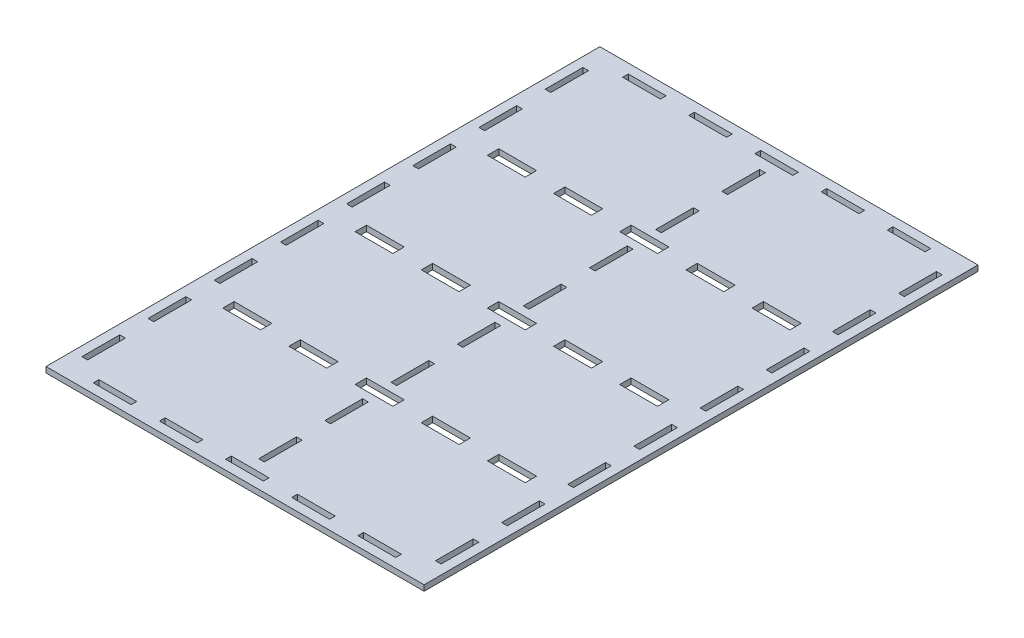
SolidWorks part; units mm, degrees
ref_plane "Front Plane" through (0, 0, 0) normal (0, 0, 1) x (1, 0, 0)
ref_plane "Top Plane" through (0, 0, 0) normal (0, 1, 0) x (1, 0, 0)
ref_plane "Right Plane" through (0, 0, 0) normal (1, 0, 0) x (0, 0, -1)
sketch "Sketch1" plane through (0, 0, 0) normal (0, 1, 0) x (1, 0, 0)
  line L1 (0, 0) -> (200, 0)
  line L2 (0, 0) -> (0, 293)
  line L3 (0, 293) -> (200, 293)
  line L4 (200, 0) -> (200, 293)
  line L5 (0, 0) -> (200, 293) construction
  line L6 (0, 293) -> (200, 0) construction
  line L7 (20, 288) -> (40, 288)
  line L8 (20, 288) -> (20, 285)
  line L9 (20, 285) -> (40, 285)
  line L10 (40, 288) -> (40, 285)
  line L11 (20, 288) -> (40, 285) construction
  line L12 (20, 285) -> (40, 288) construction
  line L13 (5, 279) -> (8, 279)
  line L14 (5, 279) -> (5, 259)
  line L15 (5, 259) -> (8, 259)
  line L16 (8, 279) -> (8, 259)
  line L17 (5, 279) -> (8, 259) construction
  line L18 (5, 259) -> (8, 279) construction
  line L38 (0, 146.5) -> (200, 146.5) construction
  line L39 (100, 293) -> (100, 0) construction
  point P10 (30, 286.5)
  point P15 (6.5, 269)
  dimension "D1" = 293
  dimension "D2" = 200
  dimension "D3" = 3
  dimension "D4" = 20
  dimension "D5" = 5
  dimension "D6" = 5
  dimension "D7" = 14
  dimension "D8" = 20
extrude "Boss-Extrude1" add sketch "Sketch1" along normal blind 3 contours L1 L4 L3 L2 L7 L10 L9 L8 L13 L16 L15 L14 | L10 L7 L8 L9 | L16 L13 L14 L15 region at (100.1677, 0, -146.2307) region at (30, 0, -286.5) region at (6.5, 0, -269)
sketch "Sketch2" plane through (0, 3, 0) normal (0, 1, 0) x (1, 0, 0)
  line L0 (5, 259) -> (8, 259) construction
  line L1 (8, 279) -> (8, 259) construction
  line L2 (5, 279) -> (5, 259) construction
  line L3 (5, 279) -> (8, 279) construction
  line L4 (8, 279) -> (5, 279)
  line L5 (8, 259) -> (8, 279)
  line L6 (5, 259) -> (8, 259)
  line L7 (5, 279) -> (5, 259)
  line L8 (8, 279) -> (5, 279)
  line L9 (8, 259) -> (8, 279)
  line L10 (5, 259) -> (8, 259)
  line L11 (5, 279) -> (5, 259)
  line L12 (40, 288) -> (20, 288)
  line L13 (40, 285) -> (40, 288)
  line L14 (20, 285) -> (40, 285)
  line L15 (20, 288) -> (20, 285)
  line L16 (40, 288) -> (20, 288)
  line L17 (40, 285) -> (40, 288)
  line L18 (20, 285) -> (40, 285)
  line L19 (20, 288) -> (20, 285)
  line L20 (0, 0) -> (200, 0)
  line L21 (200, 0) -> (200, 293)
  line L22 (200, 293) -> (0, 293)
  line L23 (0, 293) -> (0, 0)
  line L24 (0, 0) -> (200, 0)
  line L25 (200, 0) -> (200, 293)
  line L26 (200, 293) -> (0, 293)
  line L27 (0, 293) -> (0, 0)
  line L28 (20, 288) -> (20, 285) construction
  line L29 (40, 288) -> (40, 285) construction
  line L30 (20, 285) -> (40, 285) construction
  line L31 (20, 288) -> (40, 288) construction
  line L32 (5, 259) -> (8, 259)
  line L33 (8, 279) -> (8, 259)
  line L34 (5, 279) -> (5, 259)
  line L35 (5, 279) -> (8, 279)
  line L36 (20, 288) -> (20, 285)
  line L37 (40, 288) -> (40, 285)
  line L38 (20, 285) -> (40, 285)
  line L39 (20, 288) -> (40, 288)
  dimension "D1" = 0
  dimension "D2" = 0
  dimension "D3" = 0
extrude "Cut-Extrude2" cut sketch "Sketch2" against normal blind 10 contours L16 L19 L18 L17 | L8 L11 L10 L9 region at (6.5, 3, -269) region at (30, 3, -286.5)
pattern_linear "LPattern3" count 5 spacing 35 along (1, 0, 0) count 5 spacing 70 along (0, 0, 1) of face at (30, 1.5, -285) of face at (20, 1.5, -286.5) of face at (30, 1.5, -288) of face at (40, 1.5, -286.5)
pattern_linear "LPattern4" count 3 spacing 93.5 along (1, 0, 0) count 8 spacing 35 along (0, 0, 1) of face at (5, 1.5, -269) of face at (8, 1.5, -269) of face at (6.5, 1.5, -279) of face at (6.5, 1.5, -259)
sketch "Sketch4" plane through (0, 3, 0) normal (0, 1, 0) x (1, 0, 0)
  line L0 (20, 215) -> (40, 215) construction
  line L1 (6.5, 286.5) -> (100, 286.5)
  line L2 (6.5, 286.5) -> (6.5, 216.5)
  line L3 (6.5, 216.5) -> (100, 216.5)
  line L4 (100, 286.5) -> (100, 216.5)
  line L5 (20, 8) -> (20, 5) construction
  line L6 (5, 224) -> (8, 224) construction
  line L7 (100, 293) -> (100, 0) construction
  line L8 (40, 215) -> (40, 218) construction
  line L9 (6.5, 216.5) -> (100, 216.5)
  line L10 (6.5, 216.5) -> (6.5, 146.5)
  line L11 (6.5, 146.5) -> (100, 146.5)
  line L12 (100, 216.5) -> (100, 146.5)
  line L13 (20, 218) -> (20, 215) construction
  line L14 (40, 218) -> (20, 218) construction
  line L15 (6.5, 146.5) -> (100, 146.5)
  line L16 (6.5, 146.5) -> (6.5, 76.5)
  line L17 (6.5, 76.5) -> (100, 76.5)
  line L18 (100, 146.5) -> (100, 76.5)
  line L19 (20, 215) -> (40, 215)
  line L20 (40, 215) -> (40, 218)
  line L21 (6.5, 76.5) -> (100, 76.5)
  line L22 (6.5, 76.5) -> (6.5, 6.5)
  line L23 (6.5, 6.5) -> (100, 6.5)
  line L24 (100, 76.5) -> (100, 6.5)
  line L25 (20, 218) -> (20, 215)
  line L26 (40, 218) -> (20, 218)
  line L28 (20, 219.5) -> (40, 219.5)
  line L29 (20, 219.5) -> (20, 213.5)
  line L30 (20, 213.5) -> (40, 213.5)
  line L31 (40, 219.5) -> (40, 213.5)
  point P18 (20, 6.5)
  point P27 (30, 220.9155)
  point P28 (20, 216.5)
  dimension "D1" = 7.5
  dimension "D2" = 6
extrude "Cut-Extrude3" cut sketch "Sketch4" against normal blind 10 contours L28 L31 L30 L29
pattern_linear "LPattern5" count 5 spacing 35 along (1, 0, 0) count 3 spacing 70 along (0, 0, 1) of "Cut-Extrude3"
